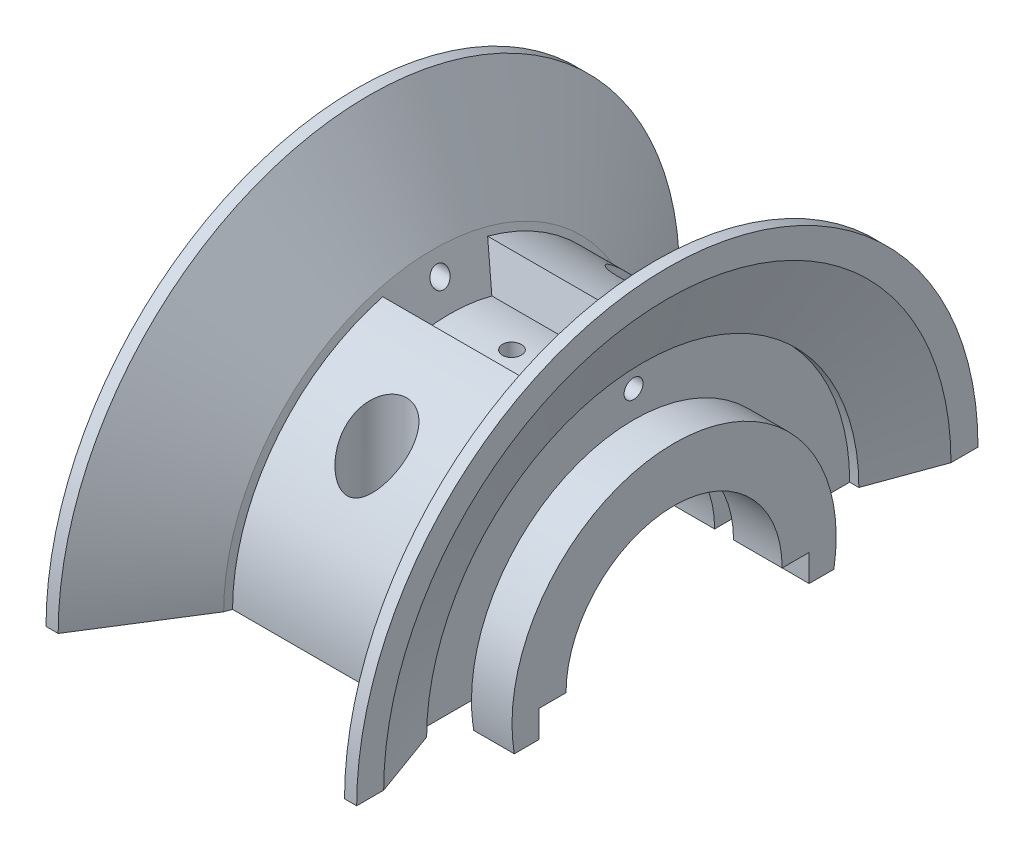
SolidWorks part; units mm, degrees
other "DifferReelA"
material "Nylon 101"
ref_plane "Front" through (0, 0, 0) normal (0, 0, 1) x (1, 0, 0)
ref_plane "Top" through (0, 0, 0) normal (0, 1, 0) x (1, 0, 0)
ref_plane "Right" through (0, 0, 0) normal (1, 0, 0) x (0, 0, -1)
ref_plane "Plane" through (0, 3, 0) normal (0, 1, 0) x (1, 0, 0)
sketch "BodySke" plane through (0, 0, 0) normal (0, 1, 0) x (1, 0, 0)
  line L0 (4.5, 0) -> (4.5, 11.5)
  line L1 (4.5, 11.5) -> (4.3, 11.5)
  line L2 (4.3, 11.5) -> (2.2982, 6)
  line L3 (2.2982, 6) -> (-2.2982, 6)
  line L4 (-2.2982, 6) -> (-4.3, 11.5)
  line L5 (-4.3, 11.5) -> (-4.5, 11.5)
  line L6 (-4.5, 11.5) -> (-4.5, 0)
  line L7 (-4.5, 0) -> (4.5, 0)
  point P2 (0, 0)
  point P9 (0, 6)
  dimension "D1" = 0.2
  dimension "D2" = 6
  dimension "D3" = 70
  dimension "D4" = 11.5
  dimension "D5" = 9
revolve "Body" add sketch "BodySke" angle 360 about L7
sketch "BoldSke" plane through (0, 0, 0) normal (0, 1, 0) x (1, 0, 0)
  line L0 (-2.2982, 6) -> (2.2982, 6)
  line L1 (2.2982, 6) -> (2.8441, 7.5)
  line L2 (4.3, 11.5) -> (2.2982, 6) construction
  line L3 (2.8441, 7.5) -> (-2.8441, 7.5)
  line L4 (-2.2982, 6) -> (-4.3, 11.5) construction
  line L5 (-2.8441, 7.5) -> (-2.2982, 6)
  line L6 (0, 0) -> (9.306, 0) construction
  dimension "D1" = 1.5
revolve "Bold" add sketch "BoldSke" angle 360 about L6
sketch "SlotSke" plane through (0, 0, 0) normal (0, 0, 1) x (1, 0, 0)
  line L0 (-2.2982, 6) -> (2.2982, 6)
  line L2 (2.2982, 6) -> (3.0261, 8)
  line L4 (3.0261, 8) -> (-3.0261, 8)
  line L6 (-3.0261, 8) -> (-2.2982, 6)
  line L7 (0, 0) -> (10.8282, 0) construction
  line L10 (0, -50) -> (0, 50) construction
  line L11 (-4.3, 11.5) -> (-4.3, -11.5) construction
  line L12 (-4.3, 11.5) -> (-2.2982, 6) construction
  line L13 (4.3, 11.5) -> (2.2982, 6) construction
  dimension "D1" = 2
  dimension "D2" = 70
  dimension "D3" = 11.5
  dimension "D4" = 6
revolve "Slot" cut sketch "SlotSke" angle 30 mid plane about L7
sketch "PadSke" plane through (0, 0, 0) normal (1, 0, 0) x (0, 0, -1)
  circle A0 centre (0, 0) radius 6
  dimension "D1" = 12
extrude "Pad" add sketch "PadSke" along normal mid plane 12
sketch "HoleSke" plane through (0, 0, 0) normal (1, 0, 0) x (0, 0, -1)
  circle A0 centre (0, 0) radius 4
  dimension "D1" = 8
extrude "Hole" cut sketch "HoleSke" against normal through all both and the other way through all
sketch "ScrewHoleSke" plane through (0, 0, 0) normal (0, 1, 0) x (1, 0, 0)
  circle A0 centre (0, 0) radius 0.35
  dimension "D1" = 0.7
extrude "ScrewHole" cut sketch "ScrewHoleSke" against normal through all both and the other way through all
sketch "BoxSke" plane through (0, 0, 0) normal (0, 0, 1) x (1, 0, 0)
  line L1 (-3.5, 4) -> (3.5, 4)
  line L2 (-3.5, 4) -> (-3.5, -4)
  line L3 (-3.5, -4) -> (3.5, -4)
  line L4 (3.5, 4) -> (3.5, -4)
  line L5 (-3.5, 4) -> (3.5, -4) construction
  line L6 (-3.5, -4) -> (3.5, 4) construction
  point P0 (0, 0)
  dimension "D1" = 8
  dimension "D2" = 7
extrude "Box" cut sketch "BoxSke" against normal mid plane 7
sketch "CutSke" plane through (0, 0, 0) normal (0, 1, 0) x (1, 0, 0)
  line L1 (-13, -13) -> (13, -13)
  line L2 (-13, -13) -> (-13, 13)
  line L3 (-13, 13) -> (13, 13)
  line L4 (13, -13) -> (13, 13)
  line L5 (-13, -13) -> (13, 13) construction
  line L6 (-13, 13) -> (13, -13) construction
  point P0 (0, 0)
  dimension "D1" = 26
extrude "Cut" cut sketch "CutSke" against normal blind 20
sketch "ScrewHole2Ske" plane through (0, 0, 0) normal (0, -1, 0) x (1, 0, 0)
  line L0 (0, 6) -> (0, 4) construction
  line L2 (-6, 4) -> (6, 4) construction
  line L3 (0, -4) -> (0, -6) construction
  line L4 (6, -4) -> (-6, -4) construction
  line L7 (-6, -6) -> (6, -6) construction
  line L8 (-6, -6) -> (-6, 6) construction
  line L9 (-6, 6) -> (6, 6) construction
  line L10 (6, -6) -> (6, 6) construction
  line L11 (-6, -6) -> (6, 6) construction
  line L12 (-6, 6) -> (6, -6) construction
  circle A0 centre (0, -5) radius 0.35
  circle A1 centre (0, 0) radius 0.35 construction
  circle A2 centre (0, 5) radius 0.35
  point P8 (0, 5)
  point P20 (0, 0)
  point P21 (0, -5)
extrude "ScrewHole2" cut sketch "ScrewHole2Ske" against normal through all
sketch "Pad2Ske" plane through (0, 3, 0) normal (0, 1, 0) x (1, 0, 0)
  line L0 (-50, 0) -> (50, 0) construction
  circle A0 centre (0, 5) radius 1.1
  circle A1 centre (0, -5) radius 1.1
  dimension "D1" = 2.2
extrude "Pad2" cut sketch "Pad2Ske" along normal through all
sketch "PinSke" plane through (0, 0, 0) normal (0, -1, 0) x (1, 0, 0)
  line L0 (-4.5, 11.5) -> (-4.5, 6) construction
  line L1 (-4.5, 5) -> (-6, 5)
  line L2 (-4.5, 5) -> (-4.5, 6)
  line L3 (-4.5, 6) -> (-6, 6)
  line L4 (-6, 5) -> (-6, 6)
  line L5 (-6, 6) -> (-6, 4) construction
  line L6 (0, -50) -> (0, 50) construction
  line L7 (4.5, 6) -> (6, 6)
  line L8 (6, 5) -> (6, 6)
  line L9 (4.5, 5) -> (6, 5)
  line L10 (4.5, 5) -> (4.5, 6)
  line L11 (50, 0) -> (-50, 0) construction
  line L12 (4.5, -5) -> (4.5, -6)
  line L13 (4.5, -5) -> (6, -5)
  line L14 (6, -5) -> (6, -6)
  line L15 (4.5, -6) -> (6, -6)
  line L16 (-4.5, -6) -> (-6, -6)
  line L17 (-6, -5) -> (-6, -6)
  line L18 (-4.5, -5) -> (-6, -5)
  line L19 (-4.5, -5) -> (-4.5, -6)
  point P10 (-6, 5)
extrude "Pin" add sketch "PinSke" along normal blind 1
sketch "Pin_Ske" plane through (-6, 0, 0) normal (-1, 0, 0) x (0, 0, 1)
  line L0 (-5.9161, -1) -> (-6, -1)
  line L1 (-5, -1) -> (-6, -1) construction
  line L2 (-6, -1) -> (-6, 0)
  line L3 (5.9161, -1) -> (6, -1)
  line L4 (6, -1) -> (6, 0)
  arc A0 (5.9161, -1) -> (6, 0) centre (0, 0) ccw
  arc A1 (-6, 0) -> (-5.9161, -1) centre (0, 0) ccw
extrude "Pin_" cut sketch "Pin_Ske" against normal through all both and the other way through all
sketch "FlangeSlotSke" plane through (-3.5, 0, 0) normal (1, 0, 0) x (0, 0, -1)
  circle A0 centre (0, 0) radius 4.65
  dimension "D1" = 9.3
extrude "FlangeSlot" cut sketch "FlangeSlotSke" against normal blind 0.7
mirror "FlangeSlot2" about plane through (0, 0, 0) normal (1, 0, 0) of "FlangeSlot"
sketch "ScrewHole3Ske" plane through (-4.5, 0, 0) normal (-1, 0, 0) x (0, 0, 1)
  circle A0 centre (0, 7) radius 0.35
  dimension "D2" = 0.7
  dimension "D1" = 7
extrude "ScrewHole3" cut sketch "ScrewHole3Ske" against normal through all
sketch "EdgeSke" plane through (0, 0, 0) normal (0, 1, 0) x (1, 0, 0)
  line L1 (0, -50) -> (0, 50) construction
  line L3 (5.75, 11.5) -> (4.5, 11.5)
  line L4 (4.5, 11.5) -> (4.5, 8)
  line L5 (-5.75, 10.5) -> (-5.75, 11.5)
  line L7 (-4.8401, 8) -> (-5.75, 10.5)
  line L8 (4.5, 8) -> (4.8401, 8)
  line L9 (4.8401, 8) -> (5.75, 10.5)
  line L10 (5.75, 10.5) -> (5.75, 11.5)
  line L11 (2.8441, 7.5) -> (4.3, 11.5) construction
  line L13 (-4.5, 8) -> (-4.8401, 8)
  line L14 (-4.5, 11.5) -> (-4.5, 8)
  line L15 (-5.75, 11.5) -> (-4.5, 11.5)
  line L17 (6, -6) -> (6, 6) construction
  dimension "D1" = 1
  dimension "D2" = 8
  dimension "D3" = 0.25
revolve "Edge" add sketch "EdgeSke" angle 180 about L7
chamfer "Chamfer" distance 1 distance2 4 1 edges at (4.3, 11.5, 0)
chamfer "Chamfer2" distance 4 distance2 1 1 edges at (-4.3, 11.5, 0)
